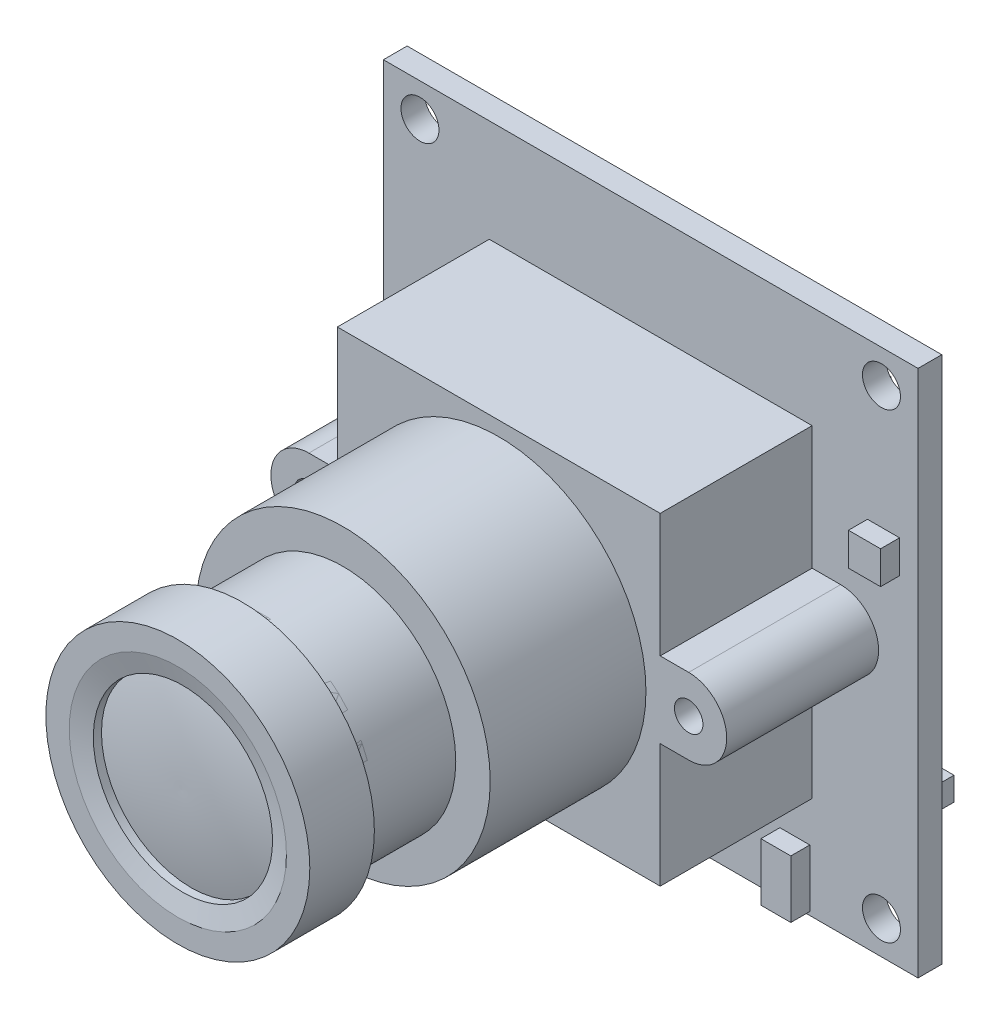
SolidWorks part; units mm, degrees
ref_plane "Front Plane" through (0, 0, 0) normal (0, 0, 1) x (1, 0, 0)
ref_plane "Top Plane" through (0, 0, 0) normal (0, 1, 0) x (1, 0, 0)
ref_plane "Right Plane" through (0, 0, 0) normal (1, 0, 0) x (0, 0, -1)
sketch "Sketch1" plane through (0, 0, 0) normal (0, 0, 1) x (1, 0, 0)
  line L1 (-14.075, 13.9) -> (14.075, 13.9)
  line L2 (-14.075, 13.9) -> (-14.075, -13.9)
  line L3 (-14.075, -13.9) -> (14.075, -13.9)
  line L4 (14.075, 13.9) -> (14.075, -13.9)
  line L5 (-14.075, 13.9) -> (14.075, -13.9) construction
  line L6 (-14.075, -13.9) -> (14.075, 13.9) construction
  point P0 (0, 0)
  dimension "D1" = 27.8
  dimension "D2" = 28.15
extrude "Base shape" add sketch "Sketch1" along normal blind 1.25
sketch "Sketch2" plane through (0, 0, 1.25) normal (0, 0, 1) x (1, 0, 0)
  line L0 (-14.075, 0) -> (14.075, 0) construction
  line L1 (-14.075, 13.9) -> (-14.075, -13.9) construction
  line L2 (14.075, -13.9) -> (14.075, 13.9) construction
  line L3 (0, 13.9) -> (0, -13.9) construction
  line L4 (14.075, 13.9) -> (-14.075, 13.9) construction
  line L5 (-14.075, -13.9) -> (14.075, -13.9) construction
  line L6 (12.15, 12.15) -> (-12.15, 12.15) construction
  line L7 (12.15, 12.15) -> (12.15, -12.15) construction
  circle A0 centre (12.15, 12.15) radius 1
  circle A1 centre (-12.15, 12.15) radius 1
  circle A2 centre (12.15, -12.15) radius 1
  circle A3 centre (-12.15, -12.15) radius 1
  point P14 (0, 12.15)
  point P16 (12.15, 0)
  dimension "D1" = 24.3
  dimension "D2" = 2
extrude "Mounting holes" cut sketch "Sketch2" against normal up to next
sketch "Sketch3" plane through (0, 0, 1.25) normal (0, 0, 1) x (1, 0, 0)
  line L0 (0, 13.9) -> (0, -13.9) construction
  line L1 (14.075, 13.9) -> (-14.075, 13.9) construction
  line L2 (-14.075, -13.9) -> (14.075, -13.9) construction
  line L3 (-14.075, 0) -> (14.075, 0) construction
  line L4 (-14.075, 13.9) -> (-14.075, -13.9) construction
  line L5 (14.075, -13.9) -> (14.075, 13.9) construction
  line L6 (-10, 0) -> (10, 0) construction
  line L7 (-8.5, 8.5) -> (8.5, 8.5)
  line L8 (-8.5, 8.5) -> (-8.5, -8.5)
  line L9 (-8.5, -8.5) -> (8.5, -8.5)
  line L10 (8.5, 8.5) -> (8.5, -8.5)
  line L11 (-8.5, 8.5) -> (8.5, -8.5) construction
  line L12 (-8.5, -8.5) -> (8.5, 8.5) construction
  line L13 (-12, 0) -> (12, 0) construction
  line L14 (-10, -2) -> (10, -2) construction
  line L15 (-10, 2) -> (-8.5, 2)
  line L16 (-10, -2) -> (-8.5, -2)
  line L17 (10, 2) -> (8.5, 2)
  line L18 (10, -2) -> (8.5, -2)
  circle A0 centre (-10, 0) radius 2
  circle A1 centre (10, 0) radius 2
  circle A2 centre (-10, 0) radius 0.75
  circle A3 centre (10, 0) radius 0.75
  point P12 (0, 0)
  point P23 (0, -2)
  dimension "D4" = 1.5
  dimension "D1" = 17
  dimension "D2" = 24
  dimension "D3" = 20
extrude "Cam base" add sketch "Sketch3" along normal blind 8 contours L8 A0 A2 | A1 L10 L7 L8 A0 L9 | A1 L10 A3 | A1 L10 L18 | L10 A1 | A1 L17 L10 | L8 A0 | A0 L8 L15 | A0 L16 L8 region at (0, 0, 1.25) region at (-8.8611, 1.8045, 1.25) region at (8.8611, 1.8045, 1.25) region at (-8.2977, 0, 1.25) region at (-8.5532, 0, 1.25) region at (9.199, 1.7744, 1.25) region at (8.2977, 0, 1.25) region at (-8.8611, -1.8045, 1.25) region at (8.8611, -1.8045, 1.25)
sketch "Sketch4" plane through (0, 0, 9.25) normal (0, 0, 1) x (1, 0, 0)
  circle A0 centre (0, 0) radius 7.75
  dimension "D1" = 15.5
extrude "Cam step 1" add sketch "Sketch4" along normal blind 8.2
sketch "Sketch5" plane through (0, 0, 17.45) normal (0, 0, 1) x (1, 0, 0)
  circle A0 centre (0, 0) radius 5.935
  dimension "D1" = 11.87
extrude "Cam step 2" add sketch "Sketch5" along normal blind 5.3
sketch "Sketch6" plane through (0, 0, 22.75) normal (0, 0, 1) x (1, 0, 0)
  circle A0 centre (0, 0) radius 6.95
  dimension "D1" = 13.9
extrude "Cam step 3" add sketch "Sketch6" along normal offset from surface (3.4 mm away) 24.9 up to face at (0, 0, 1.25) offset beyond the face yes
ref_axis "Lens axis" through (0, 0, 26.15) along (0, 0, -1)
sketch "Sketch7" plane through (0, 0, 0) normal (1, 0, 0) x (0, 0, -1)
  line L0 (-26.15, 0) -> (-9.25, 0) construction
  line L1 (-26.15, 6.95) -> (-26.15, -6.95) construction
  line L2 (-9.25, 2) -> (-9.25, -2) construction
  line L3 (-26.15, 4.72) -> (-9.25, 4.72) construction
  line L4 (-9.25, 7.75) -> (-9.25, -7.75) construction
  line L5 (-22.75, 6.95) -> (-26.15, 6.95) construction
  line L6 (-25.95, 4.72) -> (-25.95, 0) construction
  line L7 (-25.45, 0) -> (-25.45, 4.72) construction
  line L8 (-25.45, 2.36) -> (-25.95, 2.36) construction
  line L9 (-25.85, 4.72) -> (-25.85, 0) construction
  line L10 (-25.45, 4.72) -> (-26.15, 4.72)
  line L11 (-26.15, 4.72) -> (-26.15, 0)
  line L12 (-26.15, 0) -> (-25.95, 0)
  spline S0 degree 2 poles (-25.95, 0) (-25.9967, 2.3913) (-25.45, 4.72) knots 0 0 0 1 1 1
  dimension "D1" = 2.23
  dimension "D2" = 0.2
  dimension "D3" = 0.5
  dimension "D4" = 0.1
revolve "Lens profile" cut sketch "Sketch7" angle 360 about L0
chamfer "Lens chamfer" distance 1 angle 15 1 edges at (0, -4.72, 26.15) first distance on face at (0, -4.72, 26.15)
sketch "Sketch8" plane through (0, 0, 22.75) normal (0, 0, -1) x (-1, 0, 0)
  circle A0 centre (0, 0) radius 5.935 construction
  circle A1 centre (0, 0) radius 5.935
extrude "Lens background" add sketch "Sketch8" along normal blind 1 separate body
sketch "Sketch9" plane through (0, 0, 1.25) normal (0, 0, 1) x (1, 0, 0)
  line L1 (-13.2957, -8.4155) -> (-10.4905, -8.4155)
  line L2 (-13.2957, -8.4155) -> (-13.2957, -4.2269)
  line L3 (-13.2957, -4.2269) -> (-10.4905, -4.2269)
  line L4 (-10.4905, -8.4155) -> (-10.4905, -4.2269)
  line L9 (6.8015, -10.6826) -> (8.377, -10.6826)
  line L10 (6.8015, -10.6826) -> (6.8015, -13.7184)
  line L11 (6.8015, -13.7184) -> (8.377, -13.7184)
  line L12 (8.377, -10.6826) -> (8.377, -13.7184)
  line L13 (11.4128, 5.6872) -> (13.1035, 5.6872)
  line L14 (11.4128, 5.6872) -> (11.4128, 3.958)
  line L15 (11.4128, 3.958) -> (13.1035, 3.958)
  line L16 (13.1035, 5.6872) -> (13.1035, 3.958)
extrude "Front components" add sketch "Sketch9" along normal blind 1
sketch "Sketch10" plane through (0, 0, 0) normal (0, 0, -1) x (-1, 0, 0)
  line L1 (-9.9141, 5.3029) -> (-4.8033, 5.3029)
  line L2 (-9.9141, 5.3029) -> (-9.9141, 10.0678)
  line L3 (-9.9141, 10.0678) -> (-4.8033, 10.0678)
  line L4 (-4.8033, 5.3029) -> (-4.8033, 10.0678)
  line L5 (-7.5701, 2.1135) -> (-5.9946, 2.1135)
  line L6 (-7.5701, 2.1135) -> (-7.5701, 0.6533)
  line L7 (-7.5701, 0.6533) -> (-5.9946, 0.6533)
  line L8 (-5.9946, 2.1135) -> (-5.9946, 0.6533)
  line L9 (-13.2188, -6.4557) -> (-11.528, -6.4557)
  line L10 (-13.2188, -6.4557) -> (-13.2188, -7.6854)
  line L11 (-13.2188, -7.6854) -> (-11.528, -7.6854)
  line L12 (-11.528, -6.4557) -> (-11.528, -7.6854)
  line L13 (-8.9919, -9.3761) -> (-7.5316, -9.3761)
  line L14 (-8.9919, -9.3761) -> (-8.9919, -12.1044)
  line L15 (-8.9919, -12.1044) -> (-7.5316, -12.1044)
  line L16 (-7.5316, -9.3761) -> (-7.5316, -12.1044)
  line L17 (-4.7265, -4.6496) -> (-3.3047, -4.6496)
  line L18 (-4.7265, -4.6496) -> (-4.7265, -5.9177)
  line L19 (-4.7265, -5.9177) -> (-3.3047, -5.9177)
  line L20 (-3.3047, -4.6496) -> (-3.3047, -5.9177)
  line L21 (-0.0384, -5.6103) -> (1.4986, -5.6103)
  line L22 (-0.0384, -5.6103) -> (-0.0384, -8.4539)
  line L23 (-0.0384, -8.4539) -> (1.4986, -8.4539)
  line L24 (1.4986, -5.6103) -> (1.4986, -8.4539)
  line L25 (10.3752, -3.958) -> (13.1804, -3.958)
  line L26 (10.3752, -3.958) -> (10.3752, -5.6487)
  line L27 (10.3752, -5.6487) -> (13.1804, -5.6487)
  line L28 (13.1804, -3.958) -> (13.1804, -5.6487)
  line L29 (10.9132, 3.4584) -> (13.6415, 3.4584)
  line L30 (10.9132, 3.4584) -> (10.9132, 2.1519)
  line L31 (10.9132, 2.1519) -> (13.6415, 2.1519)
  line L32 (13.6415, 3.4584) -> (13.6415, 2.1519)
  line L33 (7.6854, -8.9919) -> (9.2224, -8.9919)
  line L34 (7.6854, -8.9919) -> (7.6854, -10.4137)
  line L35 (7.6854, -10.4137) -> (9.2224, -10.4137)
  line L36 (9.2224, -8.9919) -> (9.2224, -10.4137)
  line L37 (-0.7301, 2.4593) -> (6.2636, 2.4593)
  line L38 (-0.7301, 2.4593) -> (-0.7301, 9.184)
  line L39 (-0.7301, 9.184) -> (6.2636, 9.184)
  line L40 (6.2636, 2.4593) -> (6.2636, 9.184)
  circle A0 centre (-8.5692, -6.6478) radius 1.7206
  circle A1 centre (-4.2269, -8.377) radius 1.6986
extrude "Rear components" add sketch "Sketch10" along normal blind 1.5
sketch "Sketch11" plane through (0, 0, 0) normal (0, 0, -1) x (-1, 0, 0)
  line L0 (14.075, -13.9) -> (-14.075, -13.9) construction
  line L1 (0.475, -10.6) -> (10.475, -10.6)
  line L2 (0.475, -10.6) -> (0.475, -13.9)
  line L3 (0.475, -13.9) -> (10.475, -13.9)
  line L4 (10.475, -10.6) -> (10.475, -13.9)
  line L5 (14.075, 13.9) -> (14.075, -13.9) construction
  dimension "D1" = 10
  dimension "D2" = 3.3
  dimension "D3" = 3.6
extrude "Boss-Extrude9" add sketch "Sketch11" along normal blind 4.8 separate body
sketch "Sketch12" plane through (0, 0, -4.8) normal (0, 0, -1) x (-1, 0, 0)
  line L0 (0.475, -10.6) -> (0.475, -13.9) construction
  line L1 (0.875, -11) -> (4.125, -11)
  line L2 (0.875, -11) -> (0.875, -13.5)
  line L3 (0.875, -13.5) -> (4.125, -13.5)
  line L4 (4.125, -11) -> (4.125, -13.5)
  line L5 (5.375, -11) -> (10.075, -11)
  line L6 (5.375, -11) -> (5.375, -13.5)
  line L7 (5.375, -13.5) -> (10.075, -13.5)
  line L8 (10.075, -11) -> (10.075, -13.5)
  line L9 (0.875, -12.25) -> (0.475, -12.25) construction
  line L10 (2.5, -11) -> (2.5, -10.6) construction
  line L11 (10.075, -12.25) -> (10.475, -12.25) construction
  line L12 (10.475, -13.9) -> (10.475, -10.6) construction
  line L13 (10.475, -10.6) -> (0.475, -10.6) construction
  point P18 (2.594, -10.6)
  point P21 (4.008, -13.5)
  dimension "D1" = 0.4
  dimension "D2" = 1.25
  dimension "D3" = 4.7
extrude "Cut-Extrude2" cut sketch "Sketch12" against normal offset from surface (4.4 mm away) 0.4 up to face at (-8.4539, -9.7028, 0)
sketch "Sketch13" plane through (0, -10.6, 0) normal (0, 1, 0) x (1, 0, 0)
  line L0 (-10.475, 4.8) -> (-0.475, 4.8) construction
  line L1 (-0.875, 4.8) -> (-4.125, 4.8)
  line L2 (-0.875, 4.8) -> (-0.875, 3.2)
  line L3 (-0.875, 3.2) -> (-4.125, 3.2)
  line L4 (-4.125, 4.8) -> (-4.125, 3.2)
  line L6 (-5.375, 4.8) -> (-10.075, 4.8)
  line L7 (-5.375, 4.8) -> (-5.375, 3.2)
  line L8 (-5.375, 3.2) -> (-10.075, 3.2)
  line L9 (-10.075, 4.8) -> (-10.075, 3.2)
  point P10 (0, 0)
  point P11 (0, 0)
  point P12 (0, 0)
  point P14 (0, 0)
  point P15 (0, 0)
  point P16 (0, 0)
  point P18 (0, 0)
  dimension "D1" = 1.6
extrude "Cut-Extrude3" cut sketch "Sketch13" against normal up to next (0.4 mm away)
